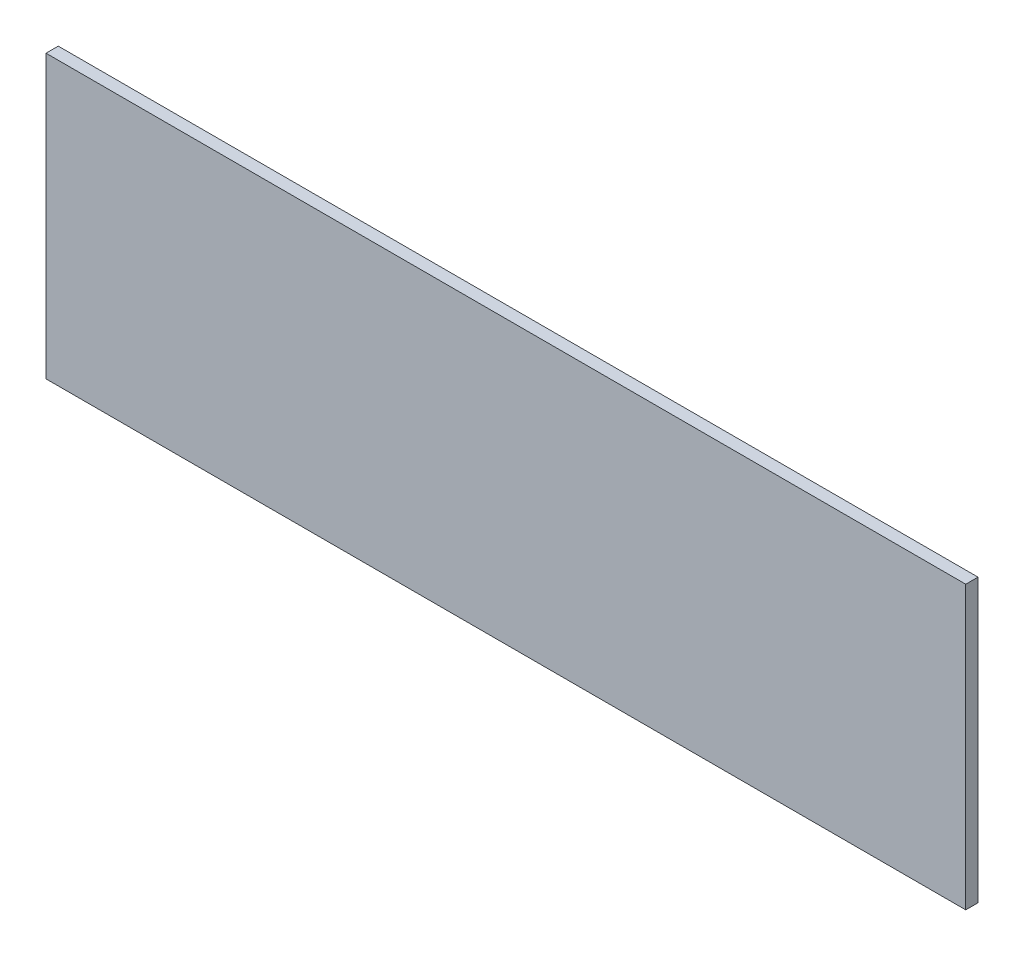
SolidWorks part; units mm, degrees
material "Pine"
ref_plane "Front Plane" through (0, 0, 0) normal (0, 0, 1) x (1, 0, 0)
ref_plane "Top Plane" through (0, 0, 0) normal (0, 1, 0) x (1, 0, 0)
ref_plane "Right Plane" through (0, 0, 0) normal (1, 0, 0) x (0, 0, -1)
sketch "Sketch1" plane through (0, 0, 0) normal (0, 0, 1) x (1, 0, 0)
  line L6 (0, 0) -> (900, 0)
  line L10 (0, 0) -> (0, 276)
  line L11 (0, 276) -> (900, 276)
  line L12 (900, 0) -> (900, 276)
  dimension "D2" = 900
  dimension "D3" = 276
extrude "Boss-Extrude1" add sketch "Sketch1" along normal blind 12 contours L10 L11 L12 L6
